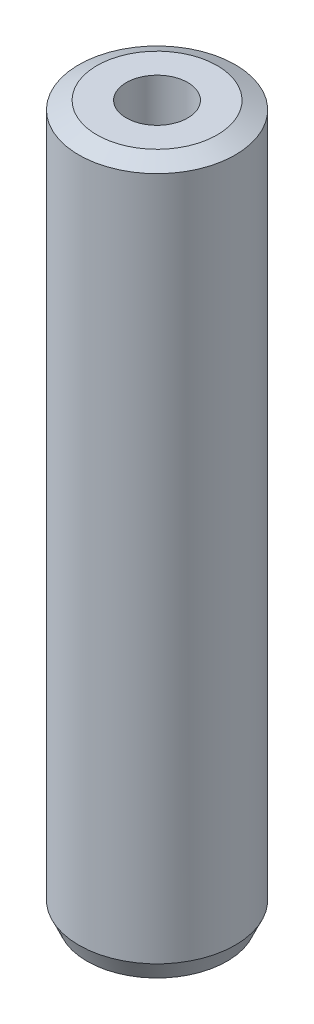
SolidWorks part; units mm, degrees
ref_plane "Front Plane" through (0, 0, 0) normal (0, 0, 1) x (1, 0, 0)
ref_plane "Top Plane" through (0, 0, 0) normal (0, 1, 0) x (1, 0, 0)
ref_plane "Right Plane" through (0, 0, 0) normal (1, 0, 0) x (0, 0, -1)
sketch "Sketch1" plane through (0, 0, 0) normal (0, 1, 0) x (1, 0, 0)
  circle A0 centre (0, 0) radius 35
  dimension "SHAFT_OD" = 70
extrude "Boss-Extrude1" add sketch "Sketch1" along normal blind 317.9444
sketch "Sketch2" plane through (0, 0, 0) normal (0, 1, 0) x (1, 0, 0)
  circle A0 centre (0, 0) radius 13.7501
  dimension "BORE_D" = 27.5002
extrude "Cut-Extrude1" cut sketch "Sketch2" along normal through all
chamfer "Chamfer1" distance 3.7095 angle 65.422 2 edges at (0, 317.9444, 35) (0, 0, 35) first distance on face at (0, 317.9444, 35) first distance on face at (0, 0, 13.7501)
